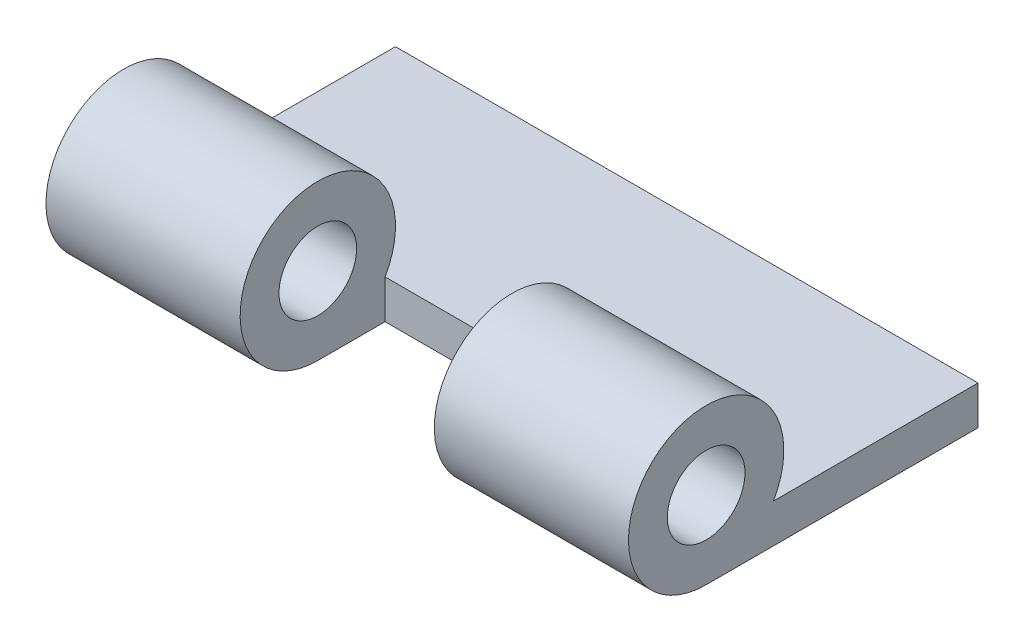
SolidWorks part; units mm, degrees
ref_plane "Ebene vorne" through (0, 0, 0) normal (0, 0, 1) x (1, 0, 0)
ref_plane "Ebene oben" through (0, 0, 0) normal (0, 1, 0) x (1, 0, 0)
ref_plane "Ebene rechts" through (0, 0, 0) normal (1, 0, 0) x (0, 0, -1)
sketch "Skizze1" plane through (0, 0, 0) normal (0, 1, 0) x (1, 0, 0)
  line L1 (0, 0) -> (15, 0)
  line L2 (0, 0) -> (0, 7)
  line L3 (0, 7) -> (15, 7)
  line L4 (15, 0) -> (15, 7)
  dimension "D1" = 15
  dimension "D2" = 7
extrude "Aufsatz-Linear austragen1" add sketch "Skizze1" along normal blind 1
sketch "Skizze2" plane through (15, 0, 0) normal (1, 0, 0) x (0, 0, -1)
  circle A0 centre (0, 2) radius 2
  circle A1 centre (0, 2) radius 1
  dimension "D1" = 2
  dimension "D2" = 1
extrude "Aufsatz-Linear austragen2" add sketch "Skizze2" against normal up to surface (15 mm away) up to face at (0, 0.5, -3.5)
ref_plane "Tangential Ebene" through (0, 0, -2) normal (0, 0, -1) x (-1, 0, 0)
sketch "Skizze8" plane through (15, 0, 0) normal (1, 0, 0) x (0, 0, -1)
  line L0 (1.7321, 1) -> (1.7321, 0)
  line L1 (1.7321, 0) -> (0, 0)
  line L3 (0, 0) -> (7, 0)
  line L4 (7, 0) -> (7, 1)
  line L5 (7, 1) -> (1.7321, 1)
  line L6 (0, 0) -> (7, 0) construction
  line L7 (7, 0) -> (7, 1) construction
  line L8 (7, 1) -> (1.7321, 1) construction
  arc A1 (1.7321, 1) -> (0, 0) centre (0, 2) ccw
  arc A2 (1.7321, 1) -> (0, 0) centre (0, 2) ccw
  dimension "D1" = 0
extrude "Schnitt-Linear austragen1" cut sketch "Skizze8" against normal blind 5 from offset 5 offset against normal yes
